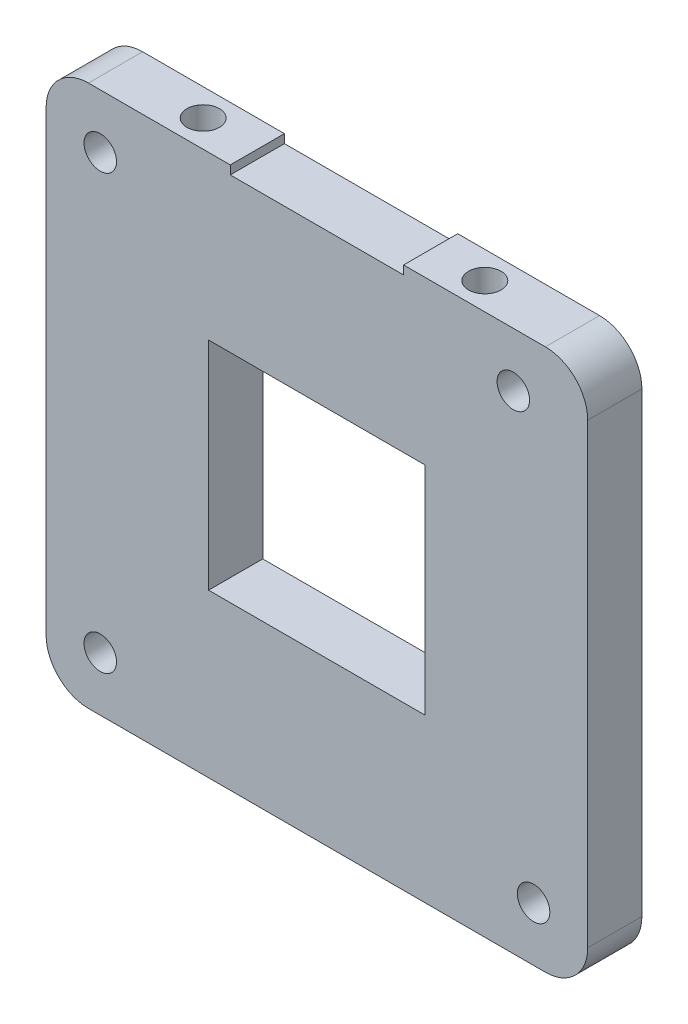
SolidWorks part; units mm, degrees
ref_plane "Front Plane" through (0, 0, 0) normal (0, 0, 1) x (1, 0, 0)
ref_plane "Top Plane" through (0, 0, 0) normal (0, 1, 0) x (1, 0, 0)
ref_plane "Right Plane" through (0, 0, 0) normal (1, 0, 0) x (0, 0, -1)
sketch "Sketch1" plane through (0, 0, 0) normal (0, 0, 1) x (1, 0, 0)
  line L0 (-21.09, 25) -> (21.09, 25)
  line L1 (-25, 21.09) -> (-25, -21.09)
  line L2 (-21.09, -25) -> (20.7574, -25)
  line L3 (25, 21.09) -> (25, -21.09)
  line L4 (21.09, -25) -> (20.7574, -25)
  arc A0 (-21.09, 25) -> (-25, 21.09) centre (-21.09, 21.09) ccw
  arc A1 (-25, -21.09) -> (-21.09, -25) centre (-21.09, -21.09) ccw
  arc A2 (21.09, 25) -> (25, 21.09) centre (21.09, 21.09) cw
  arc A3 (25, -21.09) -> (21.09, -25) centre (21.09, -21.09) cw
  point P2 (0, 25)
  point P17 (-25, 0)
  dimension "D1" = 3.91
  dimension "D2" = 42.18
  dimension "D3" = 42.18
extrude "Boss-Extrude1" add sketch "Sketch1" along normal blind 5 contours L0 A2 L3 A3 L4 L2 A1 L1 A0
sketch "Sketch2" plane through (0, 0, 5) normal (0, 0, 1) x (1, 0, 0)
  line L8 (-10, -10) -> (10, -10)
  line L9 (10, -10) -> (10, 10)
  line L10 (10, 10) -> (-10, 10)
  line L11 (-10, 10) -> (-10, -10)
  line L12 (-10, -10) -> (10, -10)
  line L13 (10, -10) -> (10, 10)
  line L14 (10, 10) -> (-10, 10)
  line L15 (-10, 10) -> (-10, -10)
  dimension "D1" = 15
extrude "Cut-Extrude1" cut sketch "Sketch2" against normal blind 5
sketch "Sketch5" plane through (0, 0, 5) normal (0, 0, 1) x (1, 0, 0)
  line L0 (-21.09, 25) -> (21.09, 25) construction
  line L1 (-25, 21.09) -> (-25, -21.09) construction
  line L3 (-21.09, -25) -> (21.09, -25) construction
  line L4 (25, 21.09) -> (25, -21.09) construction
  circle A0 centre (-20, 20) radius 1.5
  circle A1 centre (18.1305, 20) radius 1.5
  circle A2 centre (-20, -20) radius 1.5
  circle A3 centre (20, -20) radius 1.5
  dimension "D3" = 3
  dimension "D4" = 3
  dimension "D5" = 3
  dimension "D6" = 3
  dimension "D1" = 5
  dimension "D2" = 5
  dimension "D7" = 5
  dimension "D8" = 5
  dimension "D9" = 5
  dimension "D10" = 5
extrude "Cut-Extrude2" cut sketch "Sketch5" against normal through all
sketch "Sketch6" plane through (0, 0, 0) normal (0, 0, -1) x (-1, 0, 0)
  line L0 (21.09, 25) -> (-21.09, 25) construction
  line L1 (-8, 25) -> (8, 25)
  line L2 (-8, 25) -> (-8, 24.2)
  line L3 (-8, 24.2) -> (8, 24.2)
  line L4 (8, 25) -> (8, 24.2)
  point P6 (0, 24.2)
  dimension "D1" = 0.8
  dimension "D2" = 16
extrude "Cut-Extrude3" cut sketch "Sketch6" against normal through all
sketch "Sketch7" plane through (0, 25, 0) normal (0, 1, 0) x (1, 0, 0)
  line L0 (-8, -5) -> (-8, 0) construction
  line L2 (8, -5) -> (8, 0) construction
  circle A0 centre (-13, -2.5) radius 1.5
  circle A1 centre (13, -2.5) radius 1.5
  point P5 (-8, -2.5)
  point P9 (8, -2.5)
  dimension "D1" = 3
  dimension "D3" = 3
  dimension "D2" = 5
  dimension "D4" = 5
extrude "Cut-Extrude4" cut sketch "Sketch7" against normal blind 5
